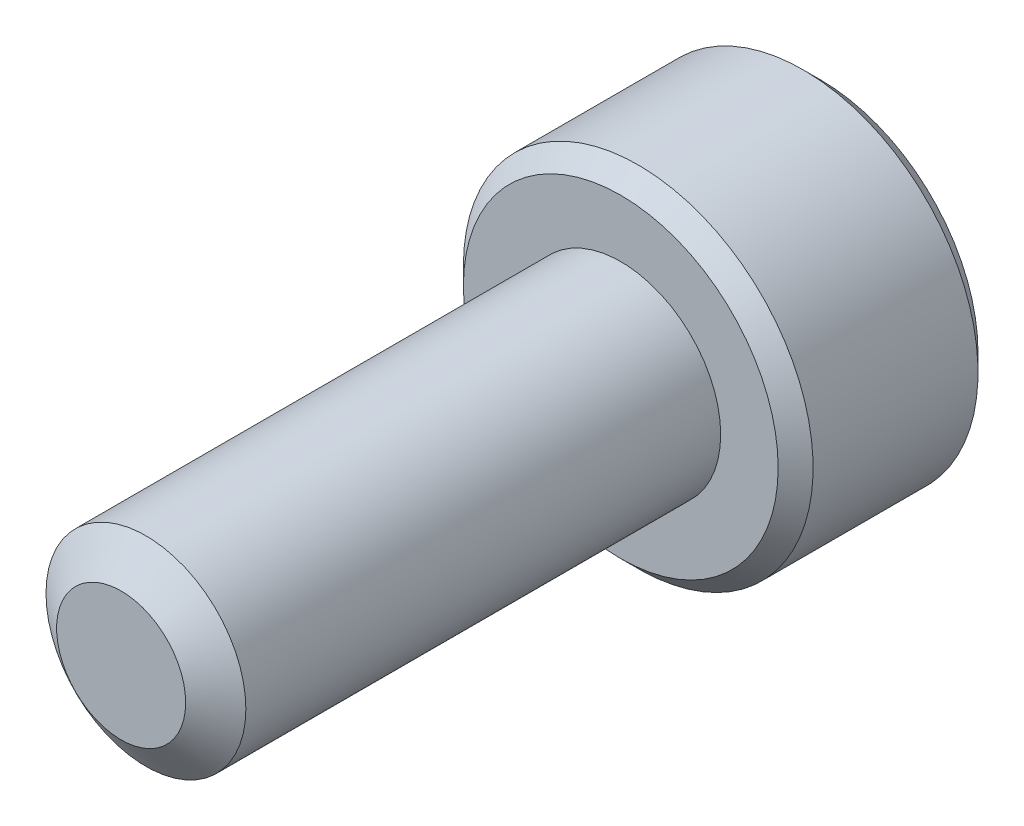
SolidWorks part; units mm, degrees
other "DetailItem1"
material "1.4310 (X10CrNi18-8)"
ref_plane "Front Plane" through (0, 0, 0) normal (0, 0, 1) x (1, 0, 0)
ref_plane "Top Plane" through (0, 0, 0) normal (0, 1, 0) x (1, 0, 0)
ref_plane "Right Plane" through (0, 0, 0) normal (1, 0, 0) x (0, 0, -1)
sketch "Sketch1" plane through (0, 0, 0) normal (0, 0, 1) x (1, 0, 0)
  circle A0 centre (0, 0) radius 2
  dimension "OD" = 4
extrude "Extrude1" add sketch "Sketch1" against normal blind 10
sketch "Sketch2" plane through (0, 0, 0) normal (0, 0, 1) x (1, 0, 0)
  circle A0 centre (0, 0) radius 2 construction
  circle A1 centre (0, 0) radius 2
curve "Helix/Spiral1" pitch 0.7 height 10.7 turns 15.2857 parameters "pitch"=0.7
sketch "Sketch3" plane through (0, 0, 0) normal (1, 0, 0) x (0, 0, -1)
  line L0 (-0.6125, 2) -> (-0.35, 1.5453)
  line L1 (-0.35, 1.5453) -> (-0.2625, 1.5453)
  line L2 (-0.2625, 1.5453) -> (0, 2)
  line L3 (-0.6125, 2) -> (0, 2)
  line L4 (-0.3062, 2) -> (-0.3062, 1.5453) construction
  line L5 (-0.4812, 1.7727) -> (-0.1312, 1.7727) construction
  line L6 (0, 2) -> (0, -2) construction
  dimension "D1" = 0.0875
  dimension "D2" = 0.35
  dimension "D3" = 60
sweep "Cut-Sweep1" [suppressed] cut profiles "Sketch3" path "Helix/Spiral1"
sketch "Sketch4" plane through (0, 0, 0) normal (1, 0, 0) x (0, 0, -1)
  line L0 (0.4962, 2) -> (0, 1.2913)
  line L1 (0, 1.2913) -> (0, 2)
  line L2 (0.4962, 2) -> (0, 2)
  line L3 (-0.6125, 2) -> (0, 2) construction
  line L4 (0, 0) -> (7.0209, 0) construction
  dimension "D1" = 55
  dimension "D2" = 0.254
revolve "Cut-Revolve1" cut sketch "Sketch4" angle 360 about L4
sketch "Sketch6" plane through (0, 0, -10) normal (0, 0, -1) x (-1, 0, 0)
  circle A0 centre (0, 0) radius 3.5
  dimension "head dia" = 7
extrude "Extrude2" add sketch "Sketch6" along normal blind 4
sketch "Sketch7" plane through (0, 0, -14) normal (0, 0, -1) x (-1, 0, 0)
  line L1 (0, 1.7321) -> (-1.5, 0.866)
  line L2 (-1.5, 0.866) -> (-1.5, -0.866)
  line L3 (-1.5, -0.866) -> (0, -1.7321)
  line L4 (0, -1.7321) -> (1.5, -0.866)
  line L5 (1.5, -0.866) -> (1.5, 0.866)
  line L6 (1.5, 0.866) -> (0, 1.7321)
  circle A0 centre (0, 0) radius 1.5 construction
  dimension "hex dia" = 3
extrude "Cut-Extrude1" cut sketch "Sketch7" against normal blind 2.25
sketch "Sketch8" plane through (0, 0, -14) normal (0, 0, -1) x (-1, 0, 0)
  circle A0 centre (0, 0) radius 1.7321
extrude "Cut-Extrude2" cut sketch "Sketch8" against normal through all draft 45
chamfer "Chamfer1" distance 0.35 angle 45 2 edges at (-3.5, 0, -14) (-3.5, 0, -10)
sketch "Sketch10" plane through (0, 0, -10) normal (0, 0, 1) x (1, 0, 0)
  circle A1 centre (0, 0) radius 2
  circle A2 centre (0, 0) radius 2
  dimension "D1" = 0
ref_plane "Plane1" through (0, 0, 0) normal (0, 0, 1) x (1, 0, 0)
extrude "partial thread" [suppressed] add sketch "Sketch10" along normal up to surface (10 mm away) separate body up to plane "Plane1"
chamfer "Chamfer2" [suppressed] distance 0.08 angle 45
combine bodies "Combine1" [suppressed] operation type add bodies to combine 107 108
sketch "Sketch9" plane through (0, 0, 0) normal (1, 0, 0) x (0, 0, -1)
  line L0 (0, 2) -> (0, -2) construction
  line L1 (1.75, 2) -> (1.75, -2) construction
  dimension "D1" = 1.75
equation "\"D3@Helix/Spiral1\" = \"screw length@Extrude1\"+\"pitch@Helix/Spiral1\""
equation "\"D1@Sketch3\" = \"pitch@Helix/Spiral1\"*.125"
equation "\"D2@Sketch3\" = \"pitch@Helix/Spiral1\"*.5"
equation "\"D1@Cut-Extrude1\" = \"hex dia@Sketch7\"*.75"
equation "\"D1@Chamfer1\" = \"head dia@Sketch6\"*.05"
equation "\"D1@Sketch9\" = \"pitch@Helix/Spiral1\"*2.5"
equation "\"D1@Chamfer2\"=\"OD@Sketch1\"*.02"
